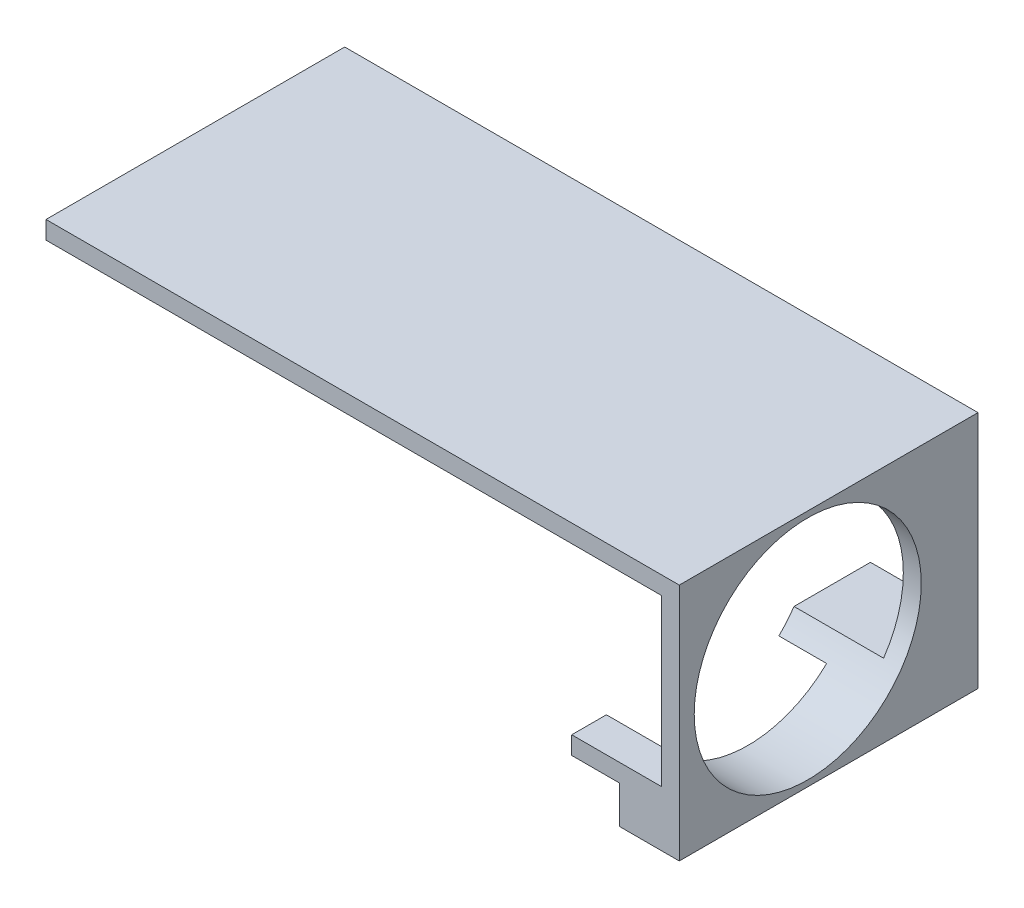
SolidWorks part; units mm, degrees
ref_plane "Front Plane" through (0, 0, 0) normal (0, 0, 1) x (1, 0, 0)
ref_plane "Top Plane" through (0, 0, 0) normal (0, 1, 0) x (1, 0, 0)
ref_plane "Right Plane" through (0, 0, 0) normal (1, 0, 0) x (0, 0, -1)
sketch "Sketch1" plane through (0, 0, 0) normal (0, 0, 1) x (1, 0, 0)
  line L0 (0, 0) -> (0, 40)
  line L1 (0, 40) -> (-106, 40)
  line L2 (-106, 40) -> (-106, 37)
  line L3 (-106, 37) -> (-3, 37)
  line L6 (0, 0) -> (-10, 0)
  line L7 (-10, 0) -> (-10, 6.3)
  line L8 (-10, 6.3) -> (-18, 6.3)
  line L9 (-18, 6.3) -> (-18, 9.3)
  line L10 (-3, 37) -> (-3, 9.3)
  line L11 (-3, 9.3) -> (-18, 9.3)
  dimension "D1" = 40
  dimension "D2" = 106
  dimension "D3" = 3
  dimension "D4" = 10
  dimension "D5" = 6.3
  dimension "D6" = 3
  dimension "D7" = 3
  dimension "D8" = 8
extrude "Boss-Extrude1" add sketch "Sketch1" along normal blind 50
sketch "Sketch2" plane through (0, 0, 0) normal (1, 0, 0) x (0, 0, -1)
  line L0 (0, 0) -> (0, 40) construction
  line L1 (-50, 0) -> (0, 0) construction
  circle A0 centre (-28.5, 20) radius 19
  dimension "D1" = 38
  dimension "D2" = 28.5
  dimension "D3" = 20
extrude "Cut-Extrude1" cut sketch "Sketch2" against normal up to next
